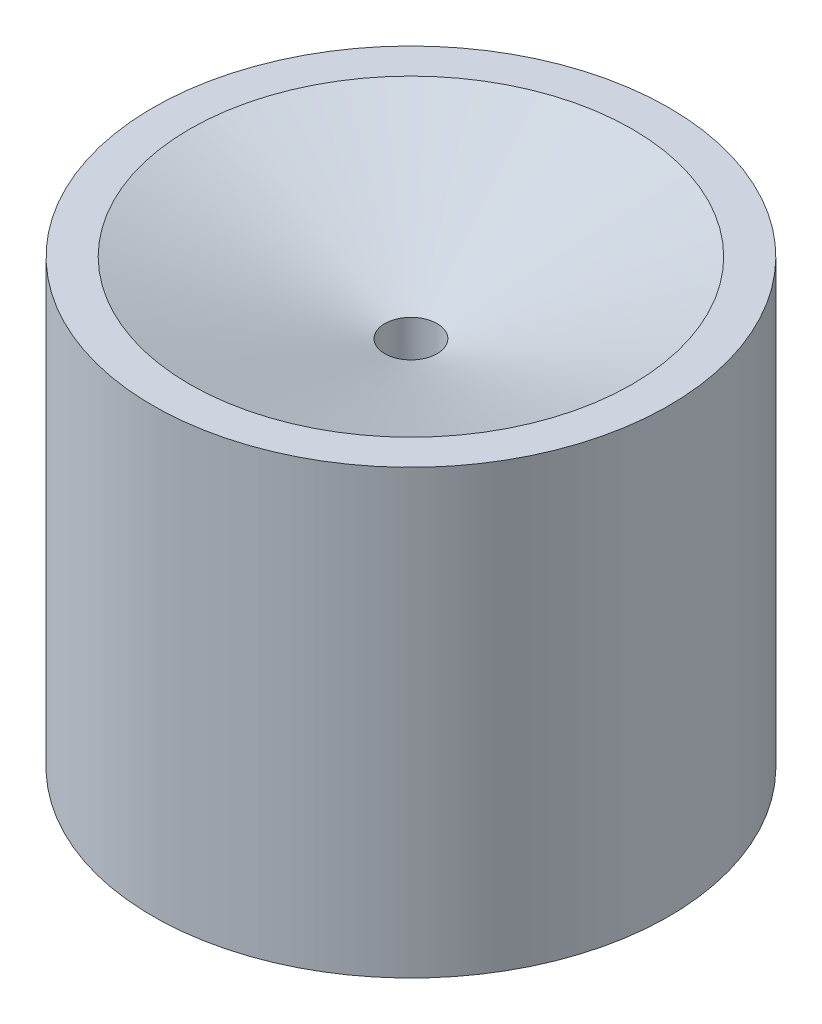
SolidWorks part; units mm, degrees
material "C (Graphite)"
ref_plane "Front Plane" through (0, 0, 0) normal (0, 0, 1) x (1, 0, 0)
ref_plane "Top Plane" through (0, 0, 0) normal (0, 1, 0) x (1, 0, 0)
ref_plane "Right Plane" through (0, 0, 0) normal (1, 0, 0) x (0, 0, -1)
sketch "Sketch1" plane through (0, 0, 0) normal (0, 0, 1) x (1, 0, 0)
  line L0 (0, 0) -> (0, 76.2) construction
  line L1 (0, 0) -> (-44.45, 0) construction
  line L2 (-44.45, 0) -> (-44.45, 76.2)
  line L4 (-4.5, 63.9706) -> (-4.5, 57.6206)
  line L5 (-4.5, 57.6206) -> (-34.925, 0)
  line L6 (-34.925, 0) -> (-44.45, 0)
  line L7 (-44.45, 76.2) -> (-38.1, 76.2)
  line L8 (-38.1, 76.2) -> (-4.5, 63.9706)
  dimension "D1" = 76.2
  dimension "D2" = 9.525
  dimension "D3" = 4.5
  dimension "D4" = 6.35
  dimension "D5" = 44.45
  dimension "D6" = 6.35
  dimension "D7" = 20
revolve "Revolve1" add sketch "Sketch1" angle 360 about L0
